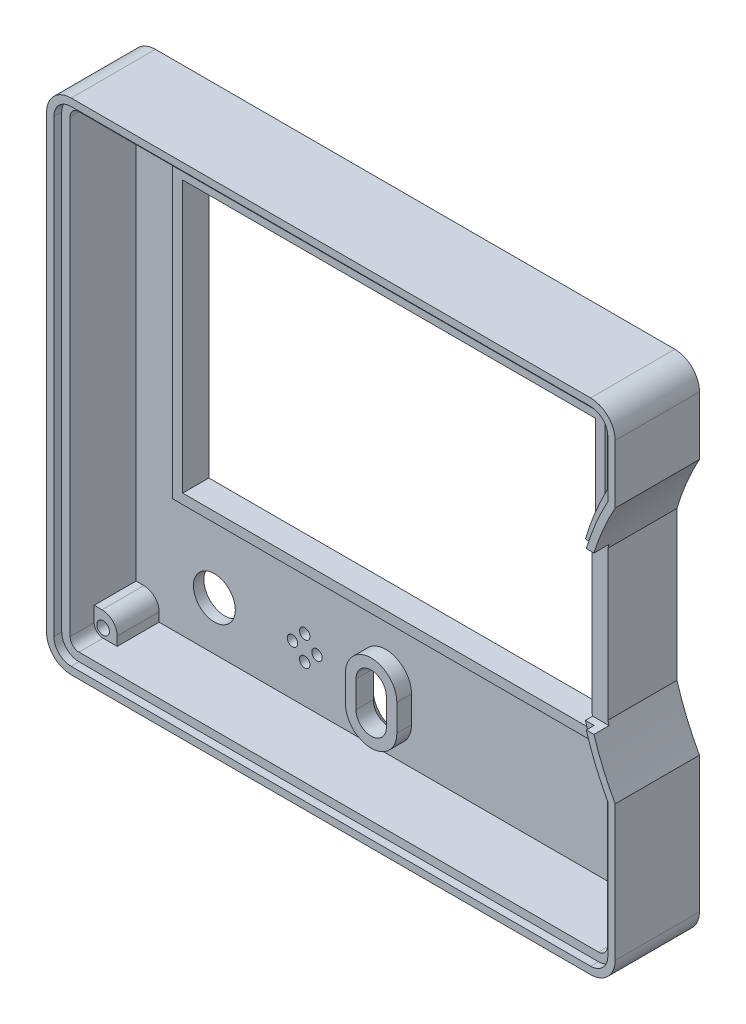
SolidWorks part; units mm, degrees
material "ABS"
ref_plane "Front Plane" through (0, 0, 0) normal (0, 0, 1) x (1, 0, 0)
ref_plane "Top Plane" through (0, 0, 0) normal (0, 1, 0) x (1, 0, 0)
ref_plane "Right Plane" through (0, 0, 0) normal (1, 0, 0) x (0, 0, -1)
sketch "Sketch1" plane through (0, 0, 0) normal (0, 0, 1) x (1, 0, 0)
  line L1 (-54.3, -47.7) -> (54.3, -47.7)
  line L2 (-54.3, -47.7) -> (-54.3, 47.7)
  line L3 (-54.3, 47.7) -> (54.3, 47.7)
  line L4 (54.3, -47.7) -> (54.3, 47.7)
  line L5 (-54.3, -47.7) -> (54.3, 47.7) construction
  line L6 (-54.3, 47.7) -> (54.3, -47.7) construction
  point P0 (0, 0)
  dimension "D1" = 108.6
  dimension "D2" = 95.4
extrude "Boss-Extrude1" add sketch "Sketch1" along normal blind 16.1
sketch "Sketch2" plane through (0, 0, 16.1) normal (0, 0, 1) x (1, 0, 0)
  line L0 (50.011, -6.8613) -> (50.011, 21.5821)
  line L1 (54.3, -47.7) -> (54.3, 47.7) construction
  line L2 (54.3, 47.7) -> (-54.3, 47.7) construction
  arc A0 (50.011, -6.8613) -> (50.011, 21.5821) centre (98.3107, 7.3604) ccw
  dimension "D1" = 100.7
  dimension "D2" = 4.289
  dimension "D3" = 40.3396
  dimension "D4" = 44.0108
extrude "Cut-Extrude1" cut sketch "Sketch2" against normal through all
fillet "Fillet1" radius 4.7 4 edges at (-54.3, -47.7, 8.05) (54.3, -47.7, 8.05) (-54.3, 47.7, 8.05) (54.3, 47.7, 8.05)
shell "Shell1" thickness 3 removed face at (17.338, 2.4535, 16.1)
sketch "Sketch3" plane through (0, 0, 16.1) normal (0, 0, 1) x (1, 0, 0)
  line L5 (-51.3, 43) -> (-51.3, -43) construction
  line L6 (49.6, 44.7) -> (-49.6, 44.7) construction
  line L7 (51.3, 32.5837) -> (51.3, 43) construction
  line L8 (-49.6, -44.7) -> (49.6, -44.7) construction
  line L9 (51.3, -43) -> (51.3, -17.8628) construction
  line L10 (-51.3, 43) -> (-51.3, -43)
  line L11 (49.6, 44.7) -> (-49.6, 44.7)
  line L12 (51.3, 32.5837) -> (51.3, 43)
  line L13 (-49.6, -44.7) -> (49.6, -44.7)
  line L14 (51.3, -43) -> (51.3, -17.8628)
  line L20 (52.9, 32.1783) -> (52.9, 43)
  line L21 (49.6, 46.3) -> (-49.6, 46.3)
  line L22 (-52.9, 43) -> (-52.9, -43)
  line L23 (-49.6, -46.3) -> (49.6, -46.3)
  line L24 (52.9, -43) -> (52.9, -17.4574)
  line L25 (48.5495, 21.5689) -> (46.8876, 21.5689)
  line L26 (48.5495, -6.8481) -> (46.8876, -6.8481)
  arc A6 (-49.6, 44.7) -> (-51.3, 43) centre (-49.6, 43) ccw construction
  arc A7 (51.3, 43) -> (49.6, 44.7) centre (49.6, 43) ccw construction
  arc A8 (-51.3, -43) -> (-49.6, -44.7) centre (-49.6, -43) ccw construction
  arc A9 (49.6, -44.7) -> (51.3, -43) centre (49.6, -43) ccw construction
  arc A10 (51.3, 32.5837) -> (47.011, 22.0082) centre (98.3107, 7.3604) ccw construction
  arc A11 (47.011, -7.2874) -> (51.3, -17.8628) centre (98.3107, 7.3604) ccw construction
  arc A12 (-49.6, 44.7) -> (-51.3, 43) centre (-49.6, 43) ccw
  arc A13 (51.3, 43) -> (49.6, 44.7) centre (49.6, 43) ccw
  arc A14 (-51.3, -43) -> (-49.6, -44.7) centre (-49.6, -43) ccw
  arc A15 (49.6, -44.7) -> (51.3, -43) centre (49.6, -43) ccw
  arc A16 (51.3, 32.5837) -> (46.8876, 21.5689) centre (98.3107, 7.3604) ccw
  arc A17 (46.8876, -6.8481) -> (51.3, -17.8628) centre (98.3107, 7.3604) ccw
  arc A22 (52.9, 32.1783) -> (48.5495, 21.5689) centre (98.3107, 7.3604) ccw
  arc A23 (52.9, 43) -> (49.6, 46.3) centre (49.6, 43) ccw
  arc A24 (-49.6, 46.3) -> (-52.9, 43) centre (-49.6, 43) ccw
  arc A25 (-52.9, -43) -> (-49.6, -46.3) centre (-49.6, -43) ccw
  arc A26 (49.6, -46.3) -> (52.9, -43) centre (49.6, -43) ccw
  arc A27 (48.5495, -6.8481) -> (52.9, -17.4574) centre (98.3107, 7.3604) ccw
  arc A28 (51.3, 32.5837) -> (47.011, 22.0082) centre (98.3107, 7.3604) ccw construction
  arc A29 (47.011, -7.2874) -> (51.3, -17.8628) centre (98.3107, 7.3604) ccw construction
  dimension "D1" = 1.6
extrude "Cut-Extrude2" cut sketch "Sketch3" against normal blind 1.5
sketch "Sketch4" plane through (0, 0, 2) normal (0, 0, 1) x (1, 0, 0)
  line L0 (-54.3, 43) -> (-54.3, -43) construction
  line L1 (-39.4, 33.7) -> (39.4, 33.7)
  line L2 (-39.4, 33.7) -> (-39.4, -18.1)
  line L3 (-39.4, -18.1) -> (39.4, -18.1)
  line L4 (39.4, 33.7) -> (39.4, -18.1)
  line L5 (49.6, 47.7) -> (-49.6, 47.7) construction
  dimension "D1" = 78.8
  dimension "D2" = 51.8
  dimension "D3" = 14.9
  dimension "D4" = 14
extrude "Cut-Extrude3" cut sketch "Sketch4" against normal through all
sketch "Sketch5" plane through (0, 0, 2) normal (0, 0, 1) x (1, 0, 0)
  line L0 (39.4, 33.7) -> (-39.4, 33.7) construction
  line L1 (39.4, -18.1) -> (39.4, 33.7) construction
  line L2 (-39.4, -18.1) -> (39.4, -18.1) construction
  line L3 (-39.4, 33.7) -> (-39.4, -18.1) construction
  line L4 (39.4, 33.7) -> (-39.4, 33.7)
  line L5 (39.4, -18.1) -> (39.4, 33.7)
  line L6 (-39.4, -18.1) -> (39.4, -18.1)
  line L7 (-39.4, 33.7) -> (-39.4, -18.1)
  line L8 (41.3, 35.6) -> (-41.3, 35.6)
  line L9 (-41.3, 35.6) -> (-41.3, -20)
  line L10 (-41.3, -20) -> (41.3, -20)
  line L11 (41.3, -20) -> (41.3, 35.6)
  dimension "D1" = 1.9
extrude "Boss-Extrude2" add sketch "Sketch5" along normal blind 3
sketch "Sketch6" plane through (0, 0, 2) normal (0, 0, 1) x (1, 0, 0)
  line L0 (-3.6, -32.4628) -> (-3.6, -37.6) construction
  line L1 (-0.7, -32.4628) -> (-0.7, -37.6)
  line L2 (-6.5, -32.4628) -> (-6.5, -37.6)
  line L3 (-49.6, -47.7) -> (49.6, -47.7) construction
  line L4 (-54.3, 43) -> (-54.3, -43) construction
  line L5 (-21.4306, -35.0338) -> (-19.09, -32.6932) construction
  line L6 (-19.09, -32.6932) -> (-16.7494, -35.0338) construction
  line L7 (-16.7494, -35.0338) -> (-19.09, -37.3744) construction
  line L8 (-19.09, -37.3744) -> (-21.4306, -35.0338) construction
  circle A0 centre (-36.35, -35.4) radius 4
  circle A1 centre (-19.09, -32.6932) radius 1
  circle A2 centre (-19.09, -37.3744) radius 1
  circle A3 centre (-21.4306, -35.0338) radius 1
  circle A4 centre (-16.7494, -35.0338) radius 1
  arc A5 (-0.7, -32.4628) -> (-6.5, -32.4628) centre (-3.6, -32.4628) ccw
  arc A6 (-6.5, -37.6) -> (-0.7, -37.6) centre (-3.6, -37.6) ccw
  point P12 (-3.6, -35.0314)
  dimension "D1" = 8
  dimension "D2" = 2
  dimension "D5" = 10.1
  dimension "D6" = 50.7
  dimension "D7" = 10.3256
  dimension "D8" = 35.21
  dimension "D9" = 4.6812
  dimension "D10" = 12.3
  dimension "D11" = 17.95
  dimension "D3" = 5.8
  dimension "D4" = 5.1372
extrude "Cut-Extrude4" cut sketch "Sketch6" against normal through all
sketch "Sketch7" plane through (0, 0, 2) normal (0, 0, 1) x (1, 0, 0)
  line L0 (-6.5, -32.4628) -> (-6.5, -37.6) construction
  line L1 (-0.7, -37.6) -> (-0.7, -32.4628) construction
  line L2 (-6.5, -32.4628) -> (-6.5, -37.6)
  line L3 (-0.7, -37.6) -> (-0.7, -32.4628)
  line L4 (-8.5, -32.4628) -> (-8.5, -37.6)
  line L5 (1.3, -37.6) -> (1.3, -32.4628)
  arc A0 (-0.7, -32.4628) -> (-6.5, -32.4628) centre (-3.6, -32.4628) ccw construction
  arc A1 (-6.5, -37.6) -> (-0.7, -37.6) centre (-3.6, -37.6) ccw construction
  arc A2 (-0.7, -32.4628) -> (-6.5, -32.4628) centre (-3.6, -32.4628) ccw
  arc A3 (-6.5, -37.6) -> (-0.7, -37.6) centre (-3.6, -37.6) ccw
  arc A4 (-8.5, -37.6) -> (1.3, -37.6) centre (-3.6, -37.6) ccw
  arc A5 (1.3, -32.4628) -> (-8.5, -32.4628) centre (-3.6, -32.4628) ccw
  dimension "D1" = 2
extrude "Boss-Extrude3" add sketch "Sketch7" along normal blind 2.8
chamfer "Chamfer1" distance 1.5 angle 45 4 edges at (-0.7, -35.0314, 0) (-3.6, -29.5628, 0) (-3.6, -40.5, 0) (-6.5, -35.0314, 0)
sketch "Sketch8" plane through (54.3, 0, 0) normal (1, 0, 0) x (0, 0, -1)
  line L0 (-16.1, -43) -> (-16.1, -17.0972) construction
  line L1 (-16.1, -7.6396) -> (-13.2, -7.6396)
  line L2 (-16.1, -7.6396) -> (-16.1, 22.3604)
  line L3 (-16.1, 22.3604) -> (-13.2, 22.3604)
  line L4 (-13.2, -7.6396) -> (-13.2, 22.3604)
  line L5 (0, 7.3604) -> (-13.2, 7.3604) construction
  line L6 (0, 21.5821) -> (0, -6.8613) construction
  dimension "D1" = 30
  dimension "D2" = 2.9
extrude "Cut-Extrude5" cut sketch "Sketch8" against normal up to next
sketch "Sketch9" plane through (0, 0, 2) normal (0, 0, 1) x (1, 0, 0)
  line L0 (49.6, 44.7) -> (-49.6, 44.7) construction
  line L1 (51.3, 32.5837) -> (51.3, 43) construction
  line L2 (49.6, 44.7) -> (46.9, 44.7)
  line L3 (-51.3, 40.1) -> (-46.9, 40.1)
  line L4 (-46.9, 44.7) -> (-46.9, 40.1)
  line L5 (51.3, 40.1) -> (51.3, 43)
  line L6 (-51.3, -43) -> (-51.3, 43) construction
  line L7 (51.3, 40.1) -> (46.9, 40.1)
  line L8 (46.9, 44.7) -> (46.9, 40.1)
  line L9 (-51.3, -43) -> (-51.3, -40.1)
  line L10 (49.6, -44.7) -> (46.9, -44.7)
  line L11 (51.3, -40.1) -> (46.9, -40.1)
  line L12 (46.9, -44.7) -> (46.9, -40.1)
  line L13 (51.3, -43) -> (51.3, -17.8628) construction
  line L14 (51.3, -43) -> (51.3, -40.1)
  line L15 (-51.3, -40.1) -> (-46.9, -40.1)
  line L16 (-46.9, -44.7) -> (-46.9, -40.1)
  line L17 (-51.3, 43) -> (-51.3, -43) construction
  line L18 (49.6, -44.7) -> (-49.6, -44.7) construction
  line L19 (51.3, -17.8628) -> (51.3, -43) construction
  line L20 (-46.9, -44.7) -> (-49.6, -44.7)
  line L21 (-51.3, 40.1) -> (-51.3, 43)
  line L22 (-46.9, 44.7) -> (-49.6, 44.7)
  arc A0 (51.3, 43) -> (49.6, 44.7) centre (49.6, 43) ccw construction
  arc A1 (51.3, 43) -> (49.6, 44.7) centre (49.6, 43) ccw
  arc A2 (-49.6, 44.7) -> (-51.3, 43) centre (-49.6, 43) ccw construction
  arc A3 (-49.6, 44.7) -> (-51.3, 43) centre (-49.6, 43) ccw
  arc A4 (-51.3, -43) -> (-49.6, -44.7) centre (-49.6, -43) ccw construction
  arc A5 (-51.3, -43) -> (-49.6, -44.7) centre (-49.6, -43) ccw
  arc A6 (49.6, -44.7) -> (51.3, -43) centre (49.6, -43) ccw construction
  arc A7 (49.6, -44.7) -> (51.3, -43) centre (49.6, -43) ccw
  dimension "D1" = 4.6
  dimension "D2" = 4.4
  dimension "D3" = 4.6
  dimension "D4" = 4.4
extrude "Boss-Extrude4" add sketch "Sketch9" along normal blind 8
fillet "Fillet2" radius 2.9 4 edges at (-46.9, 40.1, 6) (46.9, 40.1, 6) (46.9, -40.1, 6) (-46.9, -40.1, 6)
sketch "Sketch10" plane through (0, 0, 10) normal (0, 0, 1) x (1, 0, 0)
  line L0 (-54.3, 43) -> (-54.3, -43) construction
  line L1 (49.6, 47.7) -> (-49.6, 47.7) construction
  line L2 (-49.6, -47.7) -> (49.6, -47.7) construction
  line L3 (54.3, -43) -> (54.3, -17.0972) construction
  circle A0 centre (-49.6, 43) radius 1.21
  circle A1 centre (49.6, 43) radius 1.21
  circle A2 centre (49.6, -43) radius 1.21
  circle A3 centre (-49.6, -43) radius 1.21
  dimension "D1" = 2.42
  dimension "D2" = 4.7
  dimension "D3" = 4.7
  dimension "D4" = 4.7
  dimension "D5" = 4.7
extrude "Cut-Extrude6" cut sketch "Sketch10" against normal blind 9
